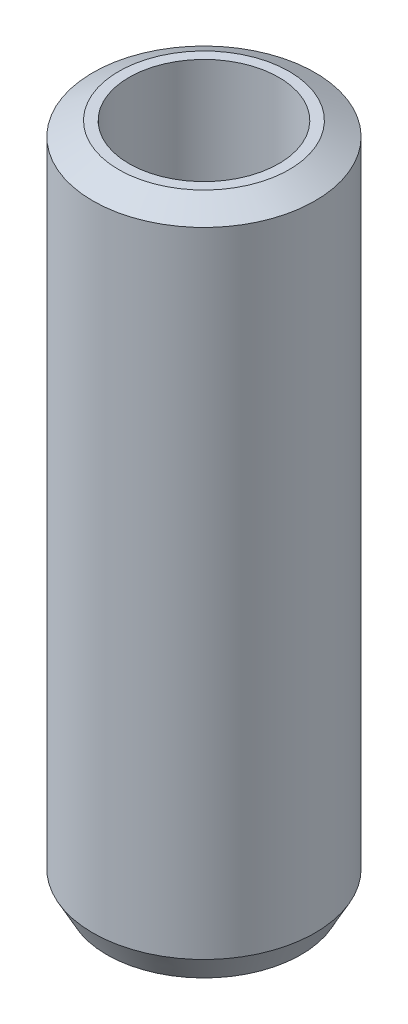
SolidWorks part; units mm, degrees
ref_plane "Front Plane" through (0, 0, 0) normal (0, 0, 1) x (1, 0, 0)
ref_plane "Top Plane" through (0, 0, 0) normal (0, 1, 0) x (1, 0, 0)
ref_plane "Right Plane" through (0, 0, 0) normal (1, 0, 0) x (0, 0, -1)
sketch "Sketch1" plane through (0, 0, 0) normal (0, 1, 0) x (1, 0, 0)
  circle A0 centre (0, 0) radius 17.5
  dimension "SHAFT_OD" = 35
extrude "Boss-Extrude1" add sketch "Sketch1" along normal blind 106.1292
sketch "Sketch2" plane through (0, 0, 0) normal (0, 1, 0) x (1, 0, 0)
  circle A0 centre (0, 0) radius 11.7904
  dimension "BORE_D" = 23.5807
extrude "Cut-Extrude1" cut sketch "Sketch2" along normal through all
chamfer "Chamfer1" distance 2.2115 angle 61.57 2 edges at (0, 106.1292, 17.5) (0, 0, 17.5) first distance on face at (0, 106.1292, 17.5) first distance on face at (0, 0, 11.7904)
